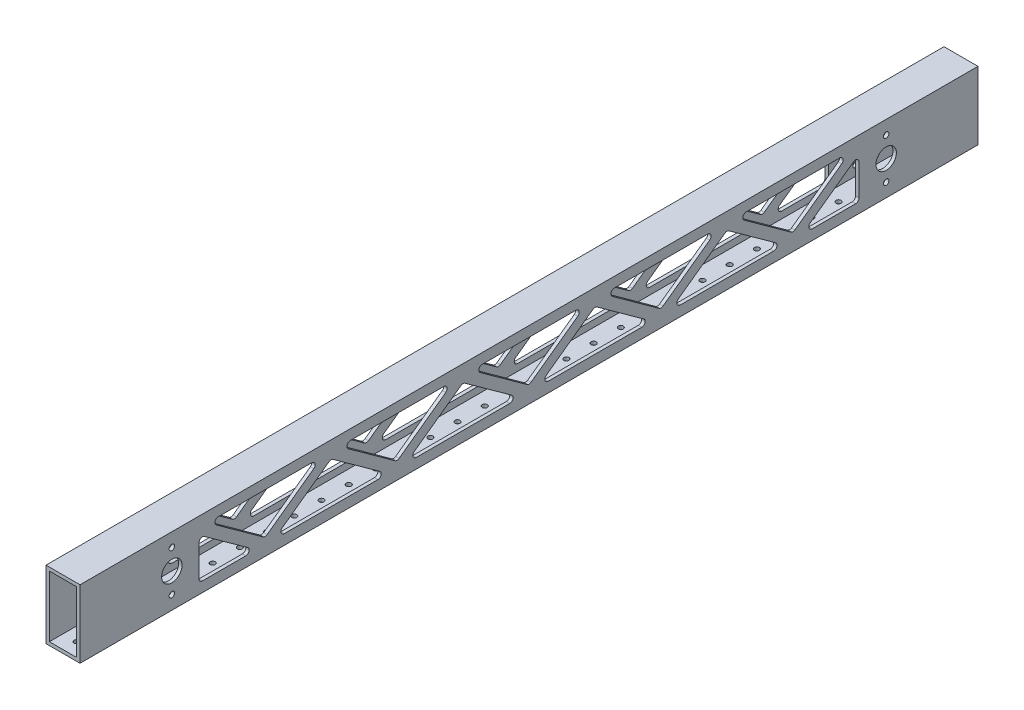
SolidWorks part; units mm, degrees
ref_plane "Front Plane" through (0, 0, 0) normal (0, 0, 1) x (1, 0, 0)
ref_plane "Top Plane" through (0, 0, 0) normal (0, 1, 0) x (1, 0, 0)
ref_plane "Right Plane" through (0, 0, 0) normal (1, 0, 0) x (0, 0, -1)
sketch "Sketch1" plane through (0, 0, 0) normal (0, 0, 1) x (1, 0, 0)
  line L1 (-12.1647, 2.5103) -> (19.5853, 2.5103)
  line L2 (-12.1647, 2.5103) -> (-12.1647, -60.9897)
  line L3 (-12.1647, -60.9897) -> (19.5853, -60.9897)
  line L4 (19.5853, 2.5103) -> (19.5853, -60.9897)
  line L5 (-8.9897, -0.6647) -> (16.4103, -0.6647)
  line L6 (-8.9897, -0.6647) -> (-8.9897, -57.8147)
  line L7 (-8.9897, -57.8147) -> (16.4103, -57.8147)
  line L8 (16.4103, -0.6647) -> (16.4103, -57.8147)
  dimension "D1" = 63.5
  dimension "D2" = 31.75
  dimension "D3" = 3.175
  dimension "D4" = 3.175
  dimension "D5" = 3.175
  dimension "D6" = 3.175
extrude "Boss-Extrude1" add sketch "Sketch1" along normal blind 838.2
sketch "Sketch2" plane through (19.5853, 0, 0) normal (1, 0, 0) x (0, 0, -1)
  line L0 (-838.2, 2.5103) -> (0, 2.5103) construction
  line L2 (-838.2, -60.9897) -> (-838.2, 2.5103) construction
  line L3 (-838.2, -60.9897) -> (0, -60.9897) construction
  line L4 (-419.1, 2.5103) -> (-419.1, -60.9897)
  circle A0 centre (-752.475, -29.2397) radius 9.525
  circle A1 centre (-752.475, -48.2897) radius 2.54
  circle A2 centre (-752.475, -10.1897) radius 2.54
  circle A3 centre (-85.725, -48.2897) radius 2.54
  circle A4 centre (-85.725, -29.2397) radius 9.525
  circle A5 centre (-85.725, -10.1897) radius 2.54
  dimension "D1" = 19.05
  dimension "D8" = 5.08
  dimension "D9" = 5.08
  dimension "D2" = 31.75
  dimension "D3" = 85.725
  dimension "D4" = 0
  dimension "D5" = 0
  dimension "D6" = 12.7
  dimension "D7" = 12.7
  dimension "D10" = 419.1
extrude "Cut-Extrude1" cut sketch "Sketch2" against normal up to surface (31.75 mm away) contours A0 | A2 | A1 | A5 | A4 | A3 up to face at (-12.1647, -29.2397, 419.1)
sketch "Sketch3" plane through (19.5853, 0, 0) normal (1, 0, 0) x (0, 0, -1)
  line L0 (-838.2, 2.5103) -> (0, 2.5103) construction
  line L1 (-736.6, 2.5103) -> (-101.6, 2.5103) construction
  line L2 (-736.6, 2.5103) -> (-736.6, -60.9897) construction
  line L3 (-736.6, -60.9897) -> (-101.6, -60.9897) construction
  line L4 (-101.6, 2.5103) -> (-101.6, -60.9897) construction
  line L5 (-838.2, -60.9897) -> (0, -60.9897) construction
  line L6 (-709.1113, -7.0147) -> (-621.8487, -7.0147)
  line L7 (-111.125, -19.0944) -> (-111.125, -48.2897)
  line L8 (-723.9, -51.4647) -> (-683.4437, -51.4647)
  line L9 (-727.075, -19.0944) -> (-727.075, -48.2897)
  line L10 (-727.075, -7.0147) -> (-665.48, -51.4647) construction
  line L11 (-665.48, -51.4647) -> (-603.885, -7.0147) construction
  line L12 (-603.885, -7.0147) -> (-542.29, -51.4647) construction
  line L13 (-542.29, -51.4647) -> (-480.695, -7.0147) construction
  line L14 (-480.695, -7.0147) -> (-419.1, -51.4647) construction
  line L15 (-419.1, -51.4647) -> (-357.505, -7.0147) construction
  line L16 (-357.505, -7.0147) -> (-295.91, -51.4647) construction
  line L17 (-295.91, -51.4647) -> (-234.315, -7.0147) construction
  line L18 (-234.315, -7.0147) -> (-172.72, -51.4647) construction
  line L19 (-172.72, -51.4647) -> (-111.125, -7.0147) construction
  line L20 (-722.042, -16.5198) -> (-681.5858, -45.7151)
  line L21 (-649.3742, -45.7151) -> (-605.743, -14.2286)
  line L22 (-602.027, -14.2286) -> (-558.3958, -45.7151)
  line L23 (-526.1842, -45.7151) -> (-482.553, -14.2286)
  line L24 (-478.837, -14.2286) -> (-435.2058, -45.7151)
  line L25 (-402.9942, -45.7151) -> (-359.363, -14.2286)
  line L26 (-355.647, -14.2286) -> (-312.0158, -45.7151)
  line L27 (-279.8042, -45.7151) -> (-236.173, -14.2286)
  line L28 (-232.457, -14.2286) -> (-188.8258, -45.7151)
  line L29 (-156.6142, -45.7151) -> (-116.158, -16.5198)
  line L30 (-710.9692, -12.7643) -> (-667.338, -44.2508)
  line L31 (-663.622, -44.2508) -> (-619.9908, -12.7643)
  line L32 (-587.7792, -12.7643) -> (-544.148, -44.2508)
  line L33 (-540.432, -44.2508) -> (-496.8008, -12.7643)
  line L34 (-464.5892, -12.7643) -> (-420.958, -44.2508)
  line L35 (-417.242, -44.2508) -> (-373.6108, -12.7643)
  line L36 (-341.3992, -12.7643) -> (-297.768, -44.2508)
  line L37 (-294.052, -44.2508) -> (-250.4208, -12.7643)
  line L38 (-218.2092, -12.7643) -> (-174.578, -44.2508)
  line L39 (-170.862, -44.2508) -> (-127.2308, -12.7643)
  line L40 (-729.8619, -10.8766) -> (-665.48, -57.3378) construction
  line L41 (-724.2881, -3.1528) -> (-665.48, -45.5916) construction
  line L42 (-665.48, -45.5916) -> (-603.885, -1.1416) construction
  line L43 (-603.885, -1.1416) -> (-542.29, -45.5916) construction
  line L44 (-542.29, -45.5916) -> (-480.695, -1.1416) construction
  line L45 (-480.695, -1.1416) -> (-419.1, -45.5916) construction
  line L46 (-419.1, -45.5916) -> (-357.505, -1.1416) construction
  line L47 (-357.505, -1.1416) -> (-295.91, -45.5916) construction
  line L48 (-295.91, -45.5916) -> (-234.315, -1.1416) construction
  line L49 (-234.315, -1.1416) -> (-172.72, -45.5916) construction
  line L50 (-172.72, -45.5916) -> (-113.9119, -3.1528) construction
  line L51 (-172.72, -57.3378) -> (-108.3381, -10.8766) construction
  line L52 (-234.315, -12.8878) -> (-172.72, -57.3378) construction
  line L53 (-357.505, -12.8878) -> (-295.91, -57.3378) construction
  line L54 (-295.91, -57.3378) -> (-234.315, -12.8878) construction
  line L55 (-480.695, -12.8878) -> (-419.1, -57.3378) construction
  line L56 (-419.1, -57.3378) -> (-357.505, -12.8878) construction
  line L57 (-542.29, -57.3378) -> (-480.695, -12.8878) construction
  line L58 (-603.885, -12.8878) -> (-542.29, -57.3378) construction
  line L59 (-665.48, -57.3378) -> (-603.885, -12.8878) construction
  line L60 (-727.075, -7.0147) -> (-111.125, -7.0147) construction
  line L61 (-727.075, -51.4647) -> (-111.125, -51.4647) construction
  line L62 (-727.075, -7.0147) -> (-727.075, -51.4647) construction
  line L63 (-647.5163, -51.4647) -> (-560.2537, -51.4647)
  line L64 (-585.9213, -7.0147) -> (-498.6587, -7.0147)
  line L65 (-524.3263, -51.4647) -> (-437.0637, -51.4647)
  line L66 (-462.7313, -7.0147) -> (-375.4687, -7.0147)
  line L67 (-401.1363, -51.4647) -> (-313.8737, -51.4647)
  line L68 (-339.5413, -7.0147) -> (-252.2787, -7.0147)
  line L69 (-277.9463, -51.4647) -> (-190.6837, -51.4647)
  line L70 (-216.3513, -7.0147) -> (-129.0887, -7.0147)
  line L71 (-154.7563, -51.4647) -> (-114.3, -51.4647)
  line L72 (-111.125, -7.0147) -> (-111.125, -51.4647) construction
  circle A0 centre (-752.475, -29.2397) radius 9.525 construction
  circle A1 centre (-85.725, -29.2397) radius 9.525 construction
  arc A2 (-602.027, -14.2286) -> (-605.743, -14.2286) centre (-603.885, -16.8032) ccw
  arc A3 (-621.8487, -7.0147) -> (-619.9908, -12.7643) centre (-621.8487, -10.1897) cw
  arc A4 (-709.1113, -7.0147) -> (-710.9692, -12.7643) centre (-709.1113, -10.1897) ccw
  arc A5 (-663.622, -44.2508) -> (-667.338, -44.2508) centre (-665.48, -41.6762) cw
  arc A6 (-683.4437, -51.4647) -> (-681.5858, -45.7151) centre (-683.4437, -48.2897) ccw
  arc A7 (-722.042, -16.5198) -> (-727.075, -19.0944) centre (-723.9, -19.0944) ccw
  arc A8 (-723.9, -51.4647) -> (-727.075, -48.2897) centre (-723.9, -48.2897) cw
  arc A9 (-114.3, -51.4647) -> (-111.125, -48.2897) centre (-114.3, -48.2897) ccw
  arc A10 (-111.125, -19.0944) -> (-116.158, -16.5198) centre (-114.3, -19.0944) ccw
  arc A11 (-154.7563, -51.4647) -> (-156.6142, -45.7151) centre (-154.7563, -48.2897) cw
  arc A12 (-174.578, -44.2508) -> (-170.862, -44.2508) centre (-172.72, -41.6762) ccw
  arc A13 (-127.2308, -12.7643) -> (-129.0887, -7.0147) centre (-129.0887, -10.1897) ccw
  arc A14 (-216.3513, -7.0147) -> (-218.2092, -12.7643) centre (-216.3513, -10.1897) ccw
  arc A15 (-279.8042, -45.7151) -> (-277.9463, -51.4647) centre (-277.9463, -48.2897) ccw
  arc A16 (-190.6837, -51.4647) -> (-188.8258, -45.7151) centre (-190.6837, -48.2897) ccw
  arc A17 (-232.457, -14.2286) -> (-236.173, -14.2286) centre (-234.315, -16.8032) ccw
  arc A18 (-252.2787, -7.0147) -> (-250.4208, -12.7643) centre (-252.2787, -10.1897) cw
  arc A19 (-294.052, -44.2508) -> (-297.768, -44.2508) centre (-295.91, -41.6762) cw
  arc A20 (-341.3992, -12.7643) -> (-339.5413, -7.0147) centre (-339.5413, -10.1897) cw
  arc A21 (-355.647, -14.2286) -> (-359.363, -14.2286) centre (-357.505, -16.8032) ccw
  arc A22 (-313.8737, -51.4647) -> (-312.0158, -45.7151) centre (-313.8737, -48.2897) ccw
  arc A23 (-401.1363, -51.4647) -> (-402.9942, -45.7151) centre (-401.1363, -48.2897) cw
  arc A24 (-373.6108, -12.7643) -> (-375.4687, -7.0147) centre (-375.4687, -10.1897) ccw
  arc A25 (-417.242, -44.2508) -> (-420.958, -44.2508) centre (-419.1, -41.6762) cw
  arc A26 (-462.7313, -7.0147) -> (-464.5892, -12.7643) centre (-462.7313, -10.1897) ccw
  arc A27 (-437.0637, -51.4647) -> (-435.2058, -45.7151) centre (-437.0637, -48.2897) ccw
  arc A28 (-478.837, -14.2286) -> (-482.553, -14.2286) centre (-480.695, -16.8032) ccw
  arc A29 (-524.3263, -51.4647) -> (-526.1842, -45.7151) centre (-524.3263, -48.2897) cw
  arc A30 (-587.7792, -12.7643) -> (-585.9213, -7.0147) centre (-585.9213, -10.1897) cw
  arc A31 (-498.6587, -7.0147) -> (-496.8008, -12.7643) centre (-498.6587, -10.1897) cw
  arc A32 (-540.432, -44.2508) -> (-544.148, -44.2508) centre (-542.29, -41.6762) cw
  arc A33 (-560.2537, -51.4647) -> (-558.3958, -45.7151) centre (-560.2537, -48.2897) ccw
  arc A34 (-649.3742, -45.7151) -> (-647.5163, -51.4647) centre (-647.5163, -48.2897) ccw
  point P93 (-164.5816, -51.4647)
  point P99 (-119.2634, -7.0147)
  point P102 (-226.1766, -7.0147)
  point P105 (-287.7716, -51.4647)
  point P108 (-180.8584, -51.4647)
  point P114 (-242.4534, -7.0147)
  point P120 (-349.3666, -7.0147)
  point P126 (-304.0484, -51.4647)
  point P129 (-410.9616, -51.4647)
  point P132 (-365.6434, -7.0147)
  point P138 (-472.5566, -7.0147)
  point P141 (-427.2384, -51.4647)
  point P147 (-534.1516, -51.4647)
  point P150 (-595.7466, -7.0147)
  point P153 (-488.8334, -7.0147)
  point P159 (-550.4284, -51.4647)
  point P162 (-657.3416, -51.4647)
  dimension "D6" = 3.175
  dimension "D7" = 3.175
  dimension "D1" = 15.875
  dimension "D2" = 15.875
  dimension "D3" = 9.525
  dimension "D4" = 4.7625
  dimension "D5" = 4.7625
extrude "Cut-Extrude2" cut sketch "Sketch3" against normal through all contours L20 L9 L8 | L30 L31 L6 | L22 L21 L8 | L32 L33 L6 | L24 L23 L8 | L34 L35 L6 | L26 L25 L8 | L36 L37 L6 | L28 L27 L8 | L38 L39 L6 | L29 L8 L7 region at (19.5853, -20.0682, 665.48) region at (19.5853, -38.5712, 128.5543) region at (19.5853, -38.5712, 709.6457) region at (19.5853, -38.4111, 603.885) region at (19.5853, -38.4111, 480.695) region at (19.5853, -38.4111, 357.505) region at (19.5853, -38.4111, 234.315) region at (19.5853, -20.0682, 542.29) region at (19.5853, -20.0682, 419.1) region at (19.5853, -20.0682, 295.91) region at (19.5853, -20.0682, 172.72)
sketch "Sketch4" plane through (0, -60.9897, 0) normal (0, -1, 0) x (1, 0, 0)
  line L0 (-12.1647, 838.2) -> (19.5853, 838.2) construction
  line L1 (19.5853, 838.2) -> (19.5853, 0) construction
  circle A0 centre (3.7103, 825.5) radius 2.3813
  circle A1 centre (3.7103, 800.1) radius 2.3813
  circle A2 centre (3.7103, 774.7) radius 2.3813
  circle A3 centre (3.7103, 749.3) radius 2.3813
  circle A4 centre (3.7103, 723.9) radius 2.3813
  circle A5 centre (3.7103, 698.5) radius 2.3813
  circle A6 centre (3.7103, 673.1) radius 2.3813
  circle A7 centre (3.7103, 647.7) radius 2.3813
  circle A8 centre (3.7103, 622.3) radius 2.3813
  circle A9 centre (3.7103, 596.9) radius 2.3813
  circle A10 centre (3.7103, 571.5) radius 2.3813
  circle A11 centre (3.7103, 546.1) radius 2.3813
  circle A12 centre (3.7103, 520.7) radius 2.3813
  circle A13 centre (3.7103, 495.3) radius 2.3813
  circle A14 centre (3.7103, 469.9) radius 2.3813
  circle A15 centre (3.7103, 444.5) radius 2.3813
  circle A16 centre (3.7103, 419.1) radius 2.3813
  circle A17 centre (3.7103, 393.7) radius 2.3813
  circle A18 centre (3.7103, 368.3) radius 2.3813
  circle A19 centre (3.7103, 342.9) radius 2.3813
  circle A20 centre (3.7103, 317.5) radius 2.3813
  circle A21 centre (3.7103, 292.1) radius 2.3813
  circle A22 centre (3.7103, 266.7) radius 2.3813
  circle A23 centre (3.7103, 241.3) radius 2.3813
  circle A24 centre (3.7103, 215.9) radius 2.3813
  circle A25 centre (3.7103, 190.5) radius 2.3813
  circle A26 centre (3.7103, 165.1) radius 2.3813
  circle A27 centre (3.7103, 139.7) radius 2.3813
  circle A28 centre (3.7103, 114.3) radius 2.3813
  circle A29 centre (3.7103, 88.9) radius 2.3813
  circle A30 centre (3.7103, 63.5) radius 2.3813
  circle A31 centre (3.7103, 38.1) radius 2.3813
  circle A32 centre (3.7103, 12.7) radius 2.3813
  dimension "D1" = 4.7625
  dimension "D2" = 12.7
  dimension "D3" = 15.875
  dimension "D4" = 33
extrude "Cut-Extrude3" cut sketch "Sketch4" against normal blind 3.175
